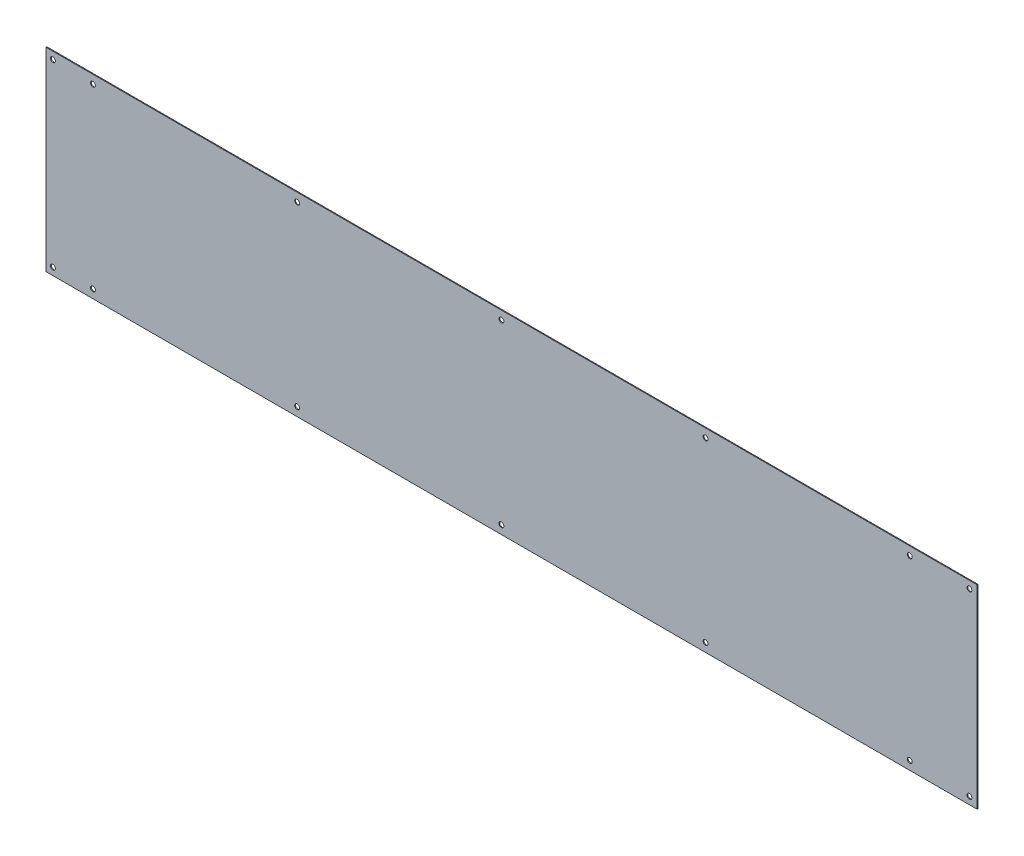
SolidWorks part; units mm, degrees
ref_plane "前视基准面" through (0, 0, 0) normal (0, 0, 1) x (1, 0, 0)
ref_plane "上视基准面" through (0, 0, 0) normal (0, 1, 0) x (1, 0, 0)
ref_plane "右视基准面" through (0, 0, 0) normal (1, 0, 0) x (0, 0, -1)
sketch "草图1" plane through (0, 0, 0) normal (0, 0, 1) x (1, 0, 0)
  line L1 (-570, 119) -> (570, 119)
  line L2 (-570, 119) -> (-570, -119)
  line L3 (-570, -119) -> (570, -119)
  line L4 (570, 119) -> (570, -119)
  line L5 (-570, 119) -> (570, -119) construction
  line L6 (-570, -119) -> (570, 119) construction
  circle A0 centre (-561.5, 110) radius 3
  circle A1 centre (-561.5, -110) radius 3
  circle A2 centre (560.5, 110) radius 3
  circle A3 centre (560.5, -110) radius 3
  point P0 (0, 0)
  dimension "D7" = 6
  dimension "D1" = 1140
  dimension "D2" = 238
  dimension "D3" = 1122
  dimension "D4" = 220
  dimension "D5" = 8.5
  dimension "D6" = 9
sheet metal parameters "钣金1" thickness 1 parameters "D1"=0.5, "厚度"=1
base flange "基体-法兰1" sketch "草图1" thickness 1 reverse thickness direction no parameters "D1"=0.5
sketch "草图3" plane through (0, 0, 0) normal (0, 0, 1) x (1, 0, 0)
  line L0 (-570, 119) -> (-570, -119) construction
  line L1 (570, 119) -> (-570, 119) construction
  circle A0 centre (-512.5, 108.5) radius 3
  circle A1 centre (-262.5, 108.5) radius 3
  circle A2 centre (-12.5, 108.5) radius 3
  circle A3 centre (237.5, 108.5) radius 3
  circle A4 centre (487.5, 108.5) radius 3
  circle A5 centre (-512.5, -108.5) radius 3
  circle A6 centre (-262.5, -108.5) radius 3
  circle A7 centre (-12.5, -108.5) radius 3
  circle A8 centre (237.5, -108.5) radius 3
  circle A9 centre (487.5, -108.5) radius 3
  dimension "D8" = 6
  dimension "D1" = 250
  dimension "D2" = 250
  dimension "D3" = 250
  dimension "D4" = 250
  dimension "D5" = 57.5
  dimension "D6" = 217
  dimension "D7" = 10.5
extrude "切除-拉伸1" cut sketch "草图3" against normal up to next normal cut yes
flat pattern "平板型式1" [suppressed]
sketch "折弯-线1" plane through (0, 0, 0) normal (0, 1, 0) x (-1, 0, 0)
